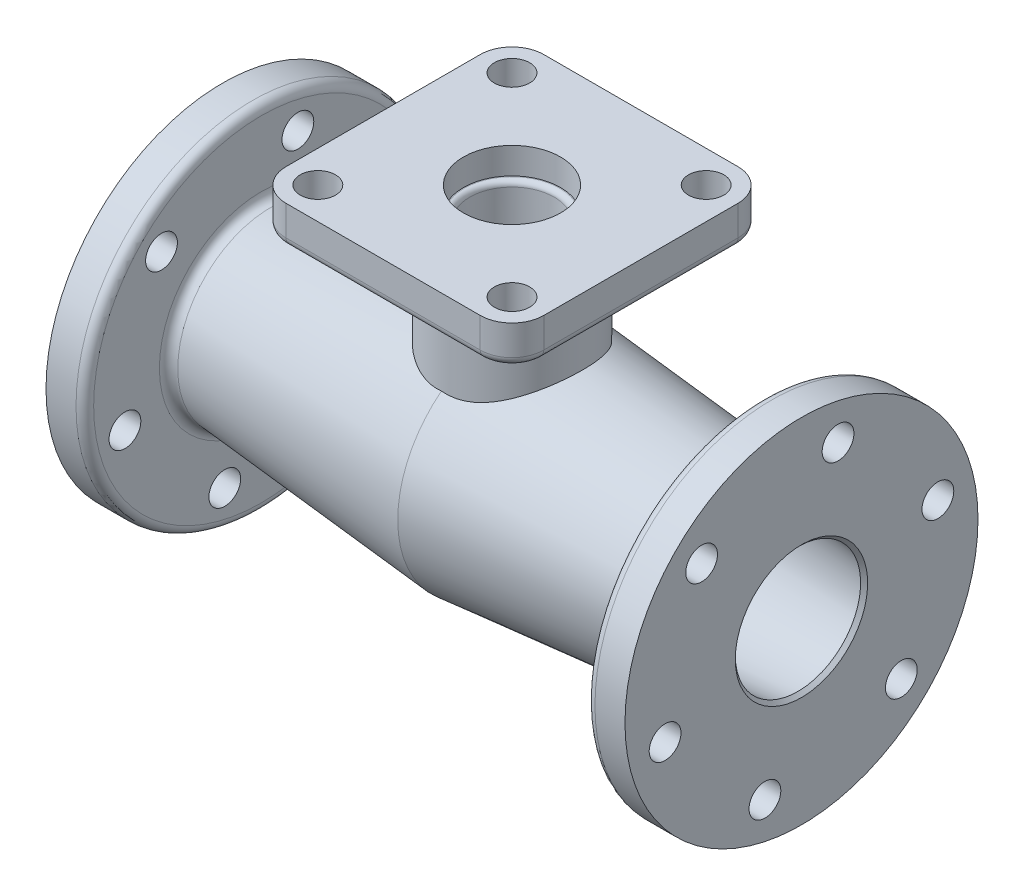
SolidWorks part; units mm, degrees
ref_plane "Front Plane" through (0, 0, 0) normal (0, 0, 1) x (1, 0, 0)
ref_plane "Top Plane" through (0, 0, 0) normal (0, 1, 0) x (1, 0, 0)
ref_plane "Right Plane" through (0, 0, 0) normal (1, 0, 0) x (0, 0, -1)
sketch "Sketch2" plane through (0, 0, 0) normal (0, 0, 1) x (1, 0, 0)
  line L0 (-164, 0) -> (164, 0) construction
  line L1 (0, 0) -> (0, 64.7305) construction
  line L2 (-164, 100) -> (-147, 100)
  line L3 (-142, 95) -> (-142, 57.7636)
  line L4 (-164, 100) -> (-164, 37.5)
  line L5 (0, 64.7305) -> (-136.5642, 52.7826)
  line L6 (-162, 35.5) -> (0, 49.6732)
  line L7 (-164, 37.5) -> (-162, 35.5)
  line L8 (164, 37.5) -> (162, 35.5)
  line L9 (162, 35.5) -> (0, 49.6732)
  line L10 (0, 64.7305) -> (136.5642, 52.7826)
  line L11 (164, 100) -> (164, 37.5)
  line L12 (142, 95) -> (142, 57.7636)
  line L13 (164, 100) -> (147, 100)
  arc A0 (-142, 57.7636) -> (-136.5642, 52.7826) centre (-137, 57.7636) ccw
  arc A1 (-142, 95) -> (-147, 100) centre (-147, 95) ccw
  arc A2 (142, 95) -> (147, 100) centre (147, 95) cw
  arc A3 (142, 57.7636) -> (136.5642, 52.7826) centre (137, 57.7636) cw
  point P14 (-142, 100)
  point P27 (142, 100)
  dimension "D7" = 5
  dimension "D1" = 328
  dimension "D2" = 22
  dimension "D3" = 100
  dimension "D4" = 2
  dimension "D5" = 5
  dimension "D6" = 15
  dimension "D8" = 45
  dimension "D9" = 37.5
revolve "Revolve1" add sketch "Sketch2" angle 360 about L0
sketch "Sketch3" plane through (0, 0, 0) normal (0, 1, 0) x (1, 0, 0)
  line L0 (0, -64.7305) -> (0, 64.7305) construction
  circle A0 centre (0, 0) radius 40
  dimension "D1" = 80
extrude "Boss-Extrude1" add sketch "Sketch3" against normal up to next from offset 110
sketch "Sketch5" plane through (0, 110, 0) normal (0, 1, 0) x (1, 0, 0)
  line L0 (0, 73) -> (0, -73) construction
  line L1 (55, 73) -> (-55, 73)
  line L2 (73, 55) -> (73, -55)
  line L3 (55, -73) -> (-55, -73)
  line L4 (-73, 55) -> (-73, -55)
  line L5 (73, 73) -> (-73, -73) construction
  line L6 (73, -73) -> (-73, 73) construction
  line L7 (-73, 0) -> (73, 0) construction
  arc A0 (73, 55) -> (55, 73) centre (55, 55) ccw
  arc A1 (73, -55) -> (55, -73) centre (55, -55) cw
  arc A2 (-73, -55) -> (-55, -73) centre (-55, -55) ccw
  arc A3 (-73, 55) -> (-55, 73) centre (-55, 55) cw
  circle A4 centre (-55, 55) radius 10
  circle A5 centre (55, 55) radius 10
  circle A6 centre (55, -55) radius 10
  circle A7 centre (-55, -55) radius 10
  point P0 (0, 0)
  dimension "D3" = 18
  dimension "D4" = 20
  dimension "D1" = 146
  dimension "D2" = 146
extrude "Boss-Extrude2" add sketch "Sketch5" along normal blind 22
sketch "Sketch6" plane through (0, 0, 0) normal (0, 0, 1) x (1, 0, 0)
  line L0 (0, 132) -> (0, -6.919) construction
  line L1 (-55, 132) -> (55, 132) construction
  line L2 (0, -64.7305) -> (0, 50.8924) construction
  line L3 (0, 132) -> (-27.5, 132)
  line L4 (-27.5, 132) -> (-27.5, 117)
  line L5 (-27.5, 117) -> (-26.9481, 117)
  line L6 (-23.9485, 114.0524) -> (-21.837, -6.919)
  line L7 (-40, 110) -> (-40, 61.2309) construction
  line L8 (-21.837, -6.919) -> (0, -6.919)
  line L9 (0, 132) -> (0, -6.919)
  arc A0 (-23.9485, 114.0524) -> (-26.9481, 117) centre (-26.9481, 114) ccw
  point P14 (-24, 117)
  dimension "D5" = 3
  dimension "D1" = 15
  dimension "D2" = 27.5
  dimension "D3" = 24
  dimension "D4" = 1
revolve "Cut-Revolve2" cut sketch "Sketch6" angle 360 about L0
sketch "Sketch7" plane through (164, 0, 0) normal (1, 0, 0) x (0, 0, -1)
  line L0 (0, 0) -> (-80, 0) construction
  line L1 (0, 0) -> (-77.2741, -20.7055) construction
  circle A0 centre (0, 0) radius 80 construction
  circle A1 centre (-77.2741, -20.7055) radius 9
  circle A3 centre (-56.5685, 56.5685) radius 9
  circle A4 centre (20.7055, 77.2741) radius 9
  circle A5 centre (77.2741, 20.7055) radius 9
  circle A6 centre (56.5685, -56.5685) radius 9
  circle A7 centre (-20.7055, -77.2741) radius 9
  point P20 (0, 0)
  dimension "D1" = 160
  dimension "D3" = 6
  dimension "D4" = 18
  dimension "D2" = 15
extrude "Cut-Extrude3" cut sketch "Sketch7" against normal blind 22
extrude "Cut-Extrude4" cut sketch "Sketch7<8>" along normal blind 22 from surface starting at face at (-164, 0, 37.5)
sketch "Sketch7<8>" plane through (164, 0, 0) normal (1, 0, 0) x (0, 0, -1) same geometry as "Sketch7"
fillet "Fillet1" radius 5 8 edges at (-67.7279, 110, 67.7279) (-73, 110, 0) (-67.7279, 110, -67.7279) (0, 110, -73) (67.7279, 110, -67.7279) (73, 110, 0) (67.7279, 110, 67.7279) (0, 110, 73)
